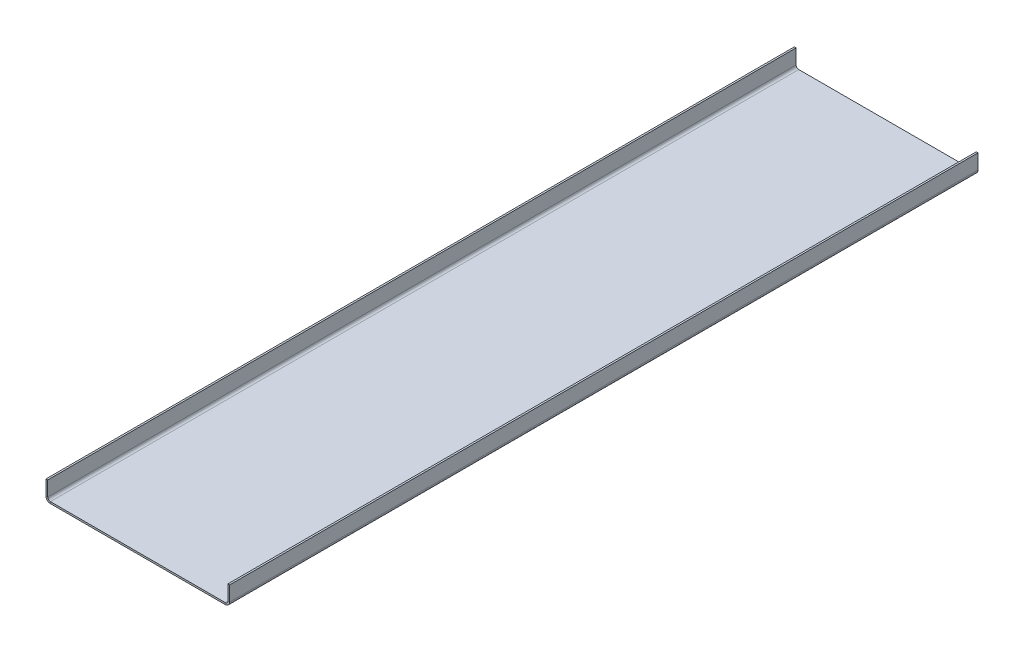
SolidWorks part; units mm, degrees
note: The reader was unsure of these and kept them because the rebuilt part matched: flange length of "Edge-Flange1".
ref_plane "Front Plane" through (0, 0, 0) normal (0, 0, 1) x (1, 0, 0)
ref_plane "Top Plane" through (0, 0, 0) normal (0, 1, 0) x (1, 0, 0)
ref_plane "Right Plane" through (0, 0, 0) normal (1, 0, 0) x (0, 0, -1)
sketch "Sketch1" plane through (0, 0, 0) normal (0, 1, 0) x (1, 0, 0)
  line L1 (100, -428) -> (-100, -428)
  line L2 (100, -428) -> (100, 428)
  line L3 (100, 428) -> (-100, 428)
  line L4 (-100, -428) -> (-100, 428)
  line L5 (100, -428) -> (-100, 428) construction
  line L6 (100, 428) -> (-100, -428) construction
  point P0 (0, 0)
  dimension "D1" = 856
  dimension "D2" = 200
base flange "Base-Flange1" sketch "Sketch1" thickness 2 reverse thickness direction no parameters "D1"=3
edge flange "Edge-Flange1" sketch "Sketch10" flange profiles "Sketch10", "Sketch11" flange angle 90 flange length 20 flange position bend outside bend radius 3 thickness 2 relief rectangular parameters "D6"=10, "D8"=1
sketch "Sketch10" plane through (100, 0, 0) normal (1, 0, 0) x (0, 0, -1)
  line L2 (-428, 0) -> (-428, 20)
  line L3 (-428, 20) -> (428, 20)
  line L4 (428, 20) -> (428, 0)
  line L7 (-428, 0) -> (428, 0) construction
  line L8 (-428, 0) -> (428, 0)
sketch "Sketch11" plane through (-100, 0, 0) normal (-1, 0, 0) x (0, 0, 1)
  line L0 (-428, 0) -> (428, 0) construction
  line L1 (-428, 0) -> (428, 0)
  line L2 (-428, 0) -> (-428, 20)
  line L3 (-428, 20) -> (428, 20)
  line L4 (428, 20) -> (428, 0)
bend "EdgeBend1" bend radius 3 bend angle 90 parameters "D5"=1
bend "EdgeBend2" bend radius 3 bend angle 90 parameters "D5"=2
sketch "Bend-Lines1" [suppressed] plane through (0, 0, 0) normal (0, 1, 0) x (1, 0, 0)
sketch "Bounding-Box1" [suppressed] plane through (0, 0, 0) normal (0, 1, 0) x (1, 0, 0)
sheet metal parameters "Sheet-Metal1" thickness 2 parameters "D1"=3
flat pattern "Flat-Pattern1" [suppressed]
sketch "Bend-Lines2" plane through (0, 0, 0) normal (0, 1, 0) x (1, 0, 0)
sketch3d "Bounding-Box2" [suppressed]
  line L0 (100, 428, 0) -> (100, -428, 0) construction
  line L1 (-100, 428, 0) -> (-100, -428, 0) construction
  line L2 (100, 428, 0) -> (-100, 428, 0) construction
  line L3 (100, -428, 0) -> (-100, -428, 0) construction
sheet metal parameters "Sheet-Metal2" thickness 2 parameters "D1"=3
flat pattern "Flat-Pattern1"
sketch "Bend-Lines2" plane through (0, 0, 0) normal (0, 1, 0) x (1, 0, 0)
  line L0 (-103.1416, 428) -> (-103.1416, -428) construction
  line L1 (103.1416, -428) -> (103.1416, 428) construction
  line L2 (-103.1416, 428) -> (-103.1416, -428) construction
  line L3 (103.1416, -428) -> (103.1416, 428) construction
sketch3d "Bounding-Box2" [suppressed]
  line L0 (-123.2832, 428, 0) -> (-123.2832, -428, 0) construction
  line L1 (123.2832, 428, 0) -> (123.2832, -428, 0) construction
  line L2 (-123.2832, 428, 0) -> (123.2832, 428, 0) construction
  line L3 (-123.2832, -428, 0) -> (123.2832, -428, 0) construction
bend of the flat pattern "Flatten-<EdgeBend1>1"
bend of the flat pattern "Flatten-<EdgeBend2>1"
